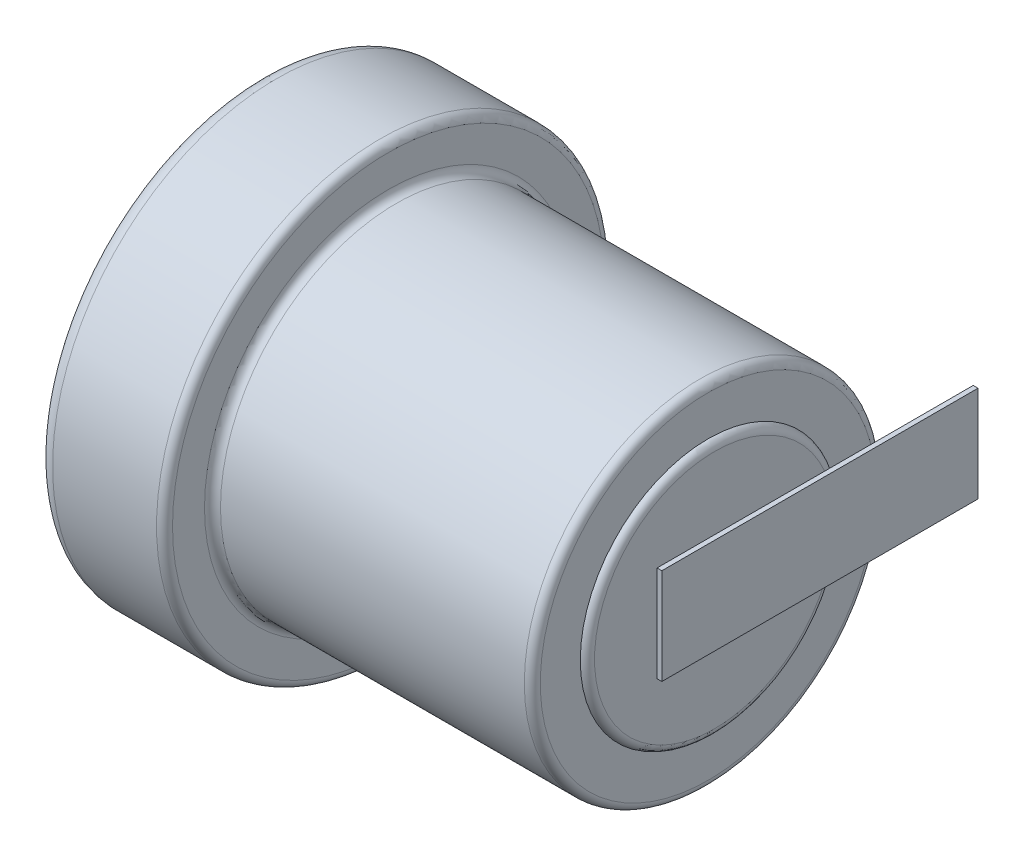
SolidWorks part; units mm, degrees
ref_plane "Front Plane" through (0, 0, 0) normal (0, 0, 1) x (1, 0, 0)
ref_plane "Top Plane" through (0, 0, 0) normal (0, 1, 0) x (1, 0, 0)
ref_plane "Right Plane" through (0, 0, 0) normal (1, 0, 0) x (0, 0, -1)
sketch "Sketch1" plane through (0, 0, 0) normal (1, 0, 0) x (0, 0, -1)
  line L0 (0, 0) -> (-7, 0)
  line L1 (55, 0) -> (-55, 0) construction
  circle A0 centre (-7, 0) radius 7
extrude "Boss-Extrude1" add sketch "Sketch1" along normal blind 4 contours A0 region at (0, 0, 13.802)
sketch "Sketch2" plane through (4, 0, 0) normal (1, 0, 0) x (0, 0, -1)
  circle A0 centre (-7, 0) radius 5.5
extrude "Boss-Extrude2" add sketch "Sketch2" along normal blind 10
sketch "Sketch3" plane through (14, 0, 0) normal (1, 0, 0) x (0, 0, -1)
  circle A0 centre (-7, 0) radius 4
extrude "Boss-Extrude3" add sketch "Sketch3" along normal blind 0.2
sketch "Sketch4" plane through (0, 0, 0) normal (-1, 0, 0) x (0, 0, 1)
  circle A0 centre (7, 0) radius 5
  circle A1 centre (7, 0) radius 4
extrude "Cut-Extrude3" cut sketch "Sketch4" against normal blind 2 contours A0 | A1
sketch "Sketch5" plane through (0, 0, 0) normal (-1, 0, 0) x (0, 0, 1)
  circle A0 centre (7, 0) radius 4
extrude "Boss-Extrude4" add sketch "Sketch5" along normal blind 0.4
fillet "Fillet1" radius 0.25 1 edges at (4, 0, 1.5)
fillet "Fillet2" radius 0.25 1 edges at (4, 0, 0)
fillet "Fillet3" radius 0.5 1 edges at (0, 0, 0)
fillet "Fillet4" radius 1 1 edges at (-0.4, 0, 11)
fillet "Fillet5" radius 0.25 2 edges at (14.2, 0, 3) (14, 0, 1.5)
sketch "Sketch6" plane through (-0.4, 0, 0) normal (-1, 0, 0) x (0, 0, 1)
  line L1 (7, -1.5) -> (8.8, -1.5)
  line L2 (8.8, -1.5) -> (8.8, 1.5)
  line L3 (8.8, 1.5) -> (5.2, 1.5)
  line L4 (5.2, 1.5) -> (5.2, -1.5)
  line L5 (5.2, -1.5) -> (7, -1.5)
extrude "Boss-Extrude5" add sketch "Sketch6" along normal blind 0.15
sketch "Sketch7" plane through (0, -1.5, 0) normal (0, -1, 0) x (1, 0, 0)
  line L0 (-0.55, 5.2) -> (-3.0956, 2.6544)
  line L2 (-2.9551, 2.5139) -> (-0.4095, 5.0595)
  line L4 (-0.4, 5.2) -> (-0.4095, 5.0595)
  line L5 (-0.55, 5.2) -> (-0.4, 5.2)
  line L6 (-2.9551, 2.5139) -> (-2.9551, -1.0861)
  line L7 (-2.9551, -1.0861) -> (-3.1551, -1.0861)
  line L8 (-3.1551, -1.0861) -> (-3.1551, 2.5139)
  line L9 (-3.1551, 2.5139) -> (-3.0956, 2.6544)
extrude "Boss-Extrude6" add sketch "Sketch7" against normal up to surface (3 mm away) up to face at (-0.475, 1.5, 7)
sketch "Sketch8" plane through (14.2, 0, 0) normal (1, 0, 0) x (0, 0, -1)
  line L1 (-7, -1.5) -> (-8.8, -1.5)
  line L2 (-8.8, -1.5) -> (-8.8, 1.5)
  line L3 (-8.8, 1.5) -> (-5.2, 1.5)
  line L4 (-5.2, 1.5) -> (-5.2, -1.5)
  line L5 (-5.2, -1.5) -> (-7, -1.5)
extrude "Boss-Extrude7" add sketch "Sketch8" along normal blind 0.15 contours L1 L2 L3 L4 L5
ref_plane "Plane1" through (-0.55, -1.5, 8.8) normal (1, 0, 0) x (0, 0, -1)
sketch "Sketch11" plane through (0, 0, 5.2) normal (0, 0, -1) x (-1, 0, 0)
  line L1 (-14.2, 1.5) -> (-14.35, 1.5)
  line L2 (-14.2, 1.5) -> (-14.2, -1.5)
  line L3 (-14.2, -1.5) -> (-14.35, -1.5)
  line L4 (-14.35, 1.5) -> (-14.35, -1.5)
extrude "Boss-Extrude8" add sketch "Sketch11" along normal up to surface (6.2861 mm away) up to face at (-3.0551, 0, -1.0861)
